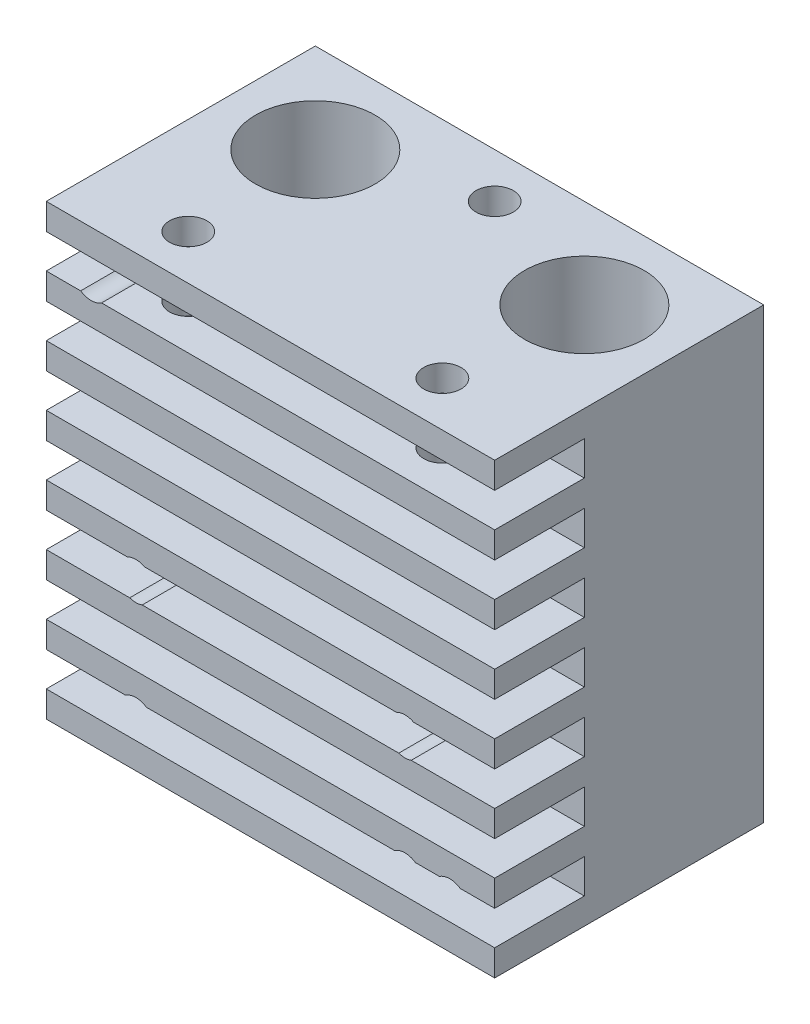
SolidWorks part; units mm, degrees
material "1060 Alloy"
ref_plane "Front Plane" through (0, 0, 0) normal (0, 0, 1) x (1, 0, 0)
ref_plane "Top Plane" through (0, 0, 0) normal (0, 1, 0) x (1, 0, 0)
ref_plane "Right Plane" through (0, 0, 0) normal (1, 0, 0) x (0, 0, -1)
sketch "Sketch1" plane through (0, 0, 0) normal (1, 0, 0) x (0, 0, -1)
  line L0 (-9, 15) -> (-9, 13.25)
  line L1 (-9, -15) -> (9, -15)
  line L2 (-9, -15) -> (-9, 15) construction
  line L3 (-9, 15) -> (9, 15)
  line L4 (9, -15) -> (9, 15)
  line L5 (-9, -15) -> (9, 15) construction
  line L6 (-9, 15) -> (9, -15) construction
  line L7 (-9, 13.25) -> (-3, 13.25)
  line L8 (-3, 13.25) -> (-3, 10.9643)
  line L9 (-3, 10.9643) -> (-9, 10.9643)
  line L10 (-9, 10.9643) -> (-9, 9.2143)
  line L11 (-9, 9.2143) -> (-3, 9.2143)
  line L12 (-3, 9.2143) -> (-3, 6.9286)
  line L13 (-3, 6.9286) -> (-9, 6.9286)
  line L14 (-9, 6.9286) -> (-9, 5.1786)
  line L15 (-9, 5.1786) -> (-3, 5.1786)
  line L16 (-3, 5.1786) -> (-3, 2.8929)
  line L17 (-3, 2.8929) -> (-9, 2.8929)
  line L18 (-9, 2.8929) -> (-9, 1.1429)
  line L19 (-9, 1.1429) -> (-3, 1.1429)
  line L20 (-3, 1.1429) -> (-3, -1.1429)
  line L21 (-3, -1.1429) -> (-9, -1.1429)
  line L22 (-9, -1.1429) -> (-9, -2.8929)
  line L23 (-9, -2.8929) -> (-3, -2.8929)
  line L24 (-3, -2.8929) -> (-3, -5.1786)
  line L25 (-3, -5.1786) -> (-9, -5.1786)
  line L26 (-9, -5.1786) -> (-9, -6.9286)
  line L27 (-9, -6.9286) -> (-3, -6.9286)
  line L28 (-3, -6.9286) -> (-3, -9.2143)
  line L29 (-3, -9.2143) -> (-9, -9.2143)
  line L30 (-9, -9.2143) -> (-9, -10.9643)
  line L31 (-9, -10.9643) -> (-3, -10.9643)
  line L32 (-3, -10.9643) -> (-3, -13.25)
  line L33 (-3, -13.25) -> (-9, -13.25)
  line L34 (-9, -13.25) -> (-9, -15)
  point P0 (0, 0)
  dimension "D1" = 30
  dimension "D2" = 18
  dimension "D3" = 6
  dimension "D4" = 1.75
extrude "Boss-Extrude1" add sketch "Sketch1" along normal mid plane 30
hole_wizard "Tap Drill for M3x0.5 Tap2" positions "Sketch22" profile "Sketch21" hole size "M3x0.5" standard "ANSI Metric"
sketch "Sketch22" plane through (0, 0, 9) normal (0, 0, 1) x (1, 0, 0)
  line L0 (15, 15) -> (-15, 15) construction
  line L3 (-15, 15) -> (-15, 13.25) construction
  line L4 (15, -10.9643) -> (15, -13.25) construction
  line L5 (15, -15) -> (-15, -15) construction
  point P0 (-12, 12)
  point P2 (12, -12)
  point P15 (-15, 14.125)
  dimension "D1" = 3
  dimension "D2" = 3
  dimension "D3" = 3
  dimension "D4" = 3
sketch "Sketch21" plane through (-12, 12, 9) normal (1, 0, 0) x (0, -1, 0)
  line L0 (0, 0) -> (0, 5.7511)
  line L1 (0, 5.7511) -> (1.25, 5)
  line L2 (1.25, 5) -> (1.25, 0)
  line L5 (1.25, 0) -> (0, 0)
  line L10 (0, 5.7511) -> (-1.25, 5) construction
  line L11 (0, -6.35) -> (0, 107.95) construction
  dimension "Hole Dia." = 2.5
  dimension "Hole Depth" = 5
  dimension "Drill Angle" = 118
hole_wizard "Ø7.0 (7) Diameter Hole1" positions "Sketch15" profile "Sketch14" hole size "Ø7.0" standard "ANSI Metric"
sketch "Sketch15" plane through (0, -15, 0) normal (0, -1, 0) x (-1, 0, 0)
  line L0 (9, 3) -> (-9, 3) construction
  line L2 (-15, 9) -> (15, 9) construction
  point P0 (9, 3)
  point P2 (-9, 3)
  point P8 (0, 3)
  dimension "D1" = 18
  dimension "D2" = 6
sketch "Sketch14" plane through (-9, -15, -3) normal (1, 0, 0) x (0, 0, -1)
  line L0 (0, 0) -> (0, 16.103)
  line L1 (0, 16.103) -> (3.5, 14)
  line L2 (3.5, 14) -> (3.5, 0)
  line L5 (3.5, 0) -> (0, 0)
  line L10 (0, 16.103) -> (-3.5, 14) construction
  line L11 (0, -6.35) -> (0, 107.95) construction
  dimension "Hole Dia." = 7
  dimension "Hole Depth" = 14
  dimension "Drill Angle" = 118
hole_wizard "Ø8.0 (8) Diameter Hole1" positions "Sketch17" profile "Sketch16" hole size "Ø8.0" standard "ANSI Metric"
sketch "Sketch17" plane through (0, 15, 0) normal (0, 1, 0) x (1, 0, 0)
  point P0 (-9, 3)
  point P3 (9, 3)
sketch "Sketch16" plane through (-9, 15, -3) normal (1, 0, 0) x (0, 0, 1)
  line L0 (0, 0) -> (0, 8.9034)
  line L1 (0, 8.9034) -> (4, 6.5)
  line L2 (4, 6.5) -> (4, 0)
  line L5 (4, 0) -> (0, 0)
  line L10 (0, 8.9034) -> (-4, 6.5) construction
  line L11 (0, -6.35) -> (0, 107.95) construction
  dimension "Hole Dia." = 8
  dimension "Hole Depth" = 6.5
  dimension "Drill Angle" = 118
hole_wizard "Ø4.2 (4.2) Diameter Hole1" positions "Sketch19" profile "Sketch20" hole size "Ø4.2" standard "ANSI Metric" end condition through all
sketch "Sketch19" plane through (0, 15, 0) normal (0, 1, 0) x (1, 0, 0)
  point P0 (-9, 3)
  point P3 (9, 3)
sketch "Sketch20" plane through (-9, 15, -3) normal (1, 0, 0) x (0, 0, 1)
  line L0 (0, 0) -> (0, 30)
  line L1 (0, 30) -> (2.1, 30)
  line L2 (2.1, 30) -> (2.1, 0)
  line L5 (2.1, 0) -> (0, 0)
  line L11 (0, -6.35) -> (0, 107.95) construction
  dimension "Thru Hole Dia." = 4.2
  dimension "Thru Hole Depth" = 30
hole_wizard "M3x0.5 Tapped Hole1" positions "Sketch9" profile "Sketch8" tap size "M3x0.5" standard "ANSI Metric" end condition through all
sketch "Sketch9" plane through (0, 0, -9) normal (0, 0, -1) x (-1, 0, 0)
  line L0 (-9, -12) -> (-9, -4) construction
  line L1 (-9, -4) -> (9, -4) construction
  line L2 (9, -4) -> (9, -12) construction
  line L3 (9, -12) -> (-9, -12) construction
  line L5 (-15, -15) -> (15, -15) construction
  point P0 (-9, -12)
  point P2 (-9, -4)
  point P4 (9, -4)
  point P6 (9, -12)
  point P20 (0, -4)
  dimension "D1" = 18
  dimension "D2" = 11
  dimension "D3" = 3
sketch "Sketch8" plane through (9, -12, -9) normal (1, 0, 0) x (0, 1, 0)
  line L0 (0, 0) -> (0, 18)
  line L1 (0, 18) -> (1.25, 18)
  line L2 (1.25, 18) -> (1.25, 0)
  line L5 (1.25, 0) -> (0, 0)
  line L11 (0, -6.35) -> (0, 107.95) construction
  dimension "Thru Tap Drill Dia." = 2.5
  dimension "Thru Tap Drill Depth" = 18
cosmetic thread "Hole Thread4" parameters "D2"=3
cosmetic thread "Hole Thread5" parameters "D2"=3
cosmetic thread "Hole Thread6" parameters "D2"=3
cosmetic thread "Hole Thread7" parameters "D2"=3
hole_wizard "M3x0.5 Tapped Hole2" positions "Sketch11" profile "Sketch10" tap size "M3x0.5" standard "ANSI Metric"
sketch "Sketch11" plane through (0, 15, 0) normal (0, 1, 0) x (1, 0, 0)
  line L0 (-8.5, -6) -> (8.5, -6) construction
  line L7 (15, -9) -> (-15, -9) construction
  line L8 (-15, 9) -> (-15, -9) construction
  line L10 (15, 9) -> (-15, 9) construction
  point P0 (-8.5, -6)
  point P2 (8.5, -6)
  point P21 (0, -6)
  point P25 (0, 6)
  dimension "D1" = 6.5
  dimension "D2" = 3
  dimension "D3" = 3
sketch "Sketch10" plane through (-8.5, 15, 6) normal (1, 0, 0) x (0, 0, 1)
  line L0 (0, 0) -> (0, 6.7511)
  line L1 (0, 6.7511) -> (1.25, 6)
  line L2 (1.25, 6) -> (1.25, 0)
  line L5 (1.25, 0) -> (0, 0)
  line L10 (0, 6.7511) -> (-1.25, 6) construction
  line L11 (0, -6.35) -> (0, 107.95) construction
  dimension "Tap Drill Dia." = 2.5
  dimension "Tap Drill Depth" = 6
  dimension "Drill Angle" = 118
cosmetic thread "Hole Thread8" parameters "D1"=5.7857, "D2"=3
cosmetic thread "Hole Thread9" parameters "D1"=5.7857, "D2"=3
cosmetic thread "Hole Thread13" parameters "D1"=6, "D2"=3
hole_wizard "M3x0.5 Tapped Hole3" positions "Sketch13" profile "Sketch12" tap size "M3x0.5" standard "ANSI Metric"
sketch "Sketch13" plane through (0, 0, -9) normal (0, 0, -1) x (-1, 0, 0)
  line L0 (-4.5, 5) -> (4.5, 5) construction
  line L2 (0, -5) -> (0, 5) construction
  line L4 (-15, 15) -> (15, 15) construction
  point P0 (-4.5, 5)
  point P2 (4.5, 5)
  point P4 (0, -5)
  dimension "D1" = 10
  dimension "D2" = 9
  dimension "D3" = 10
sketch "Sketch12" plane through (4.5, 5, -9) normal (1, 0, 0) x (0, 1, 0)
  line L0 (0, 0) -> (0, 8.7511)
  line L1 (0, 8.7511) -> (1.25, 8)
  line L2 (1.25, 8) -> (1.25, 0)
  line L5 (1.25, 0) -> (0, 0)
  line L10 (0, 8.7511) -> (-1.25, 8) construction
  line L11 (0, -6.35) -> (0, 107.95) construction
  dimension "Tap Drill Dia." = 2.5
  dimension "Tap Drill Depth" = 8
  dimension "Drill Angle" = 118
cosmetic thread "Hole Thread10" parameters "D1"=6, "D2"=3
cosmetic thread "Hole Thread11" parameters "D1"=6, "D2"=3
cosmetic thread "Hole Thread12" parameters "D1"=6, "D2"=3
